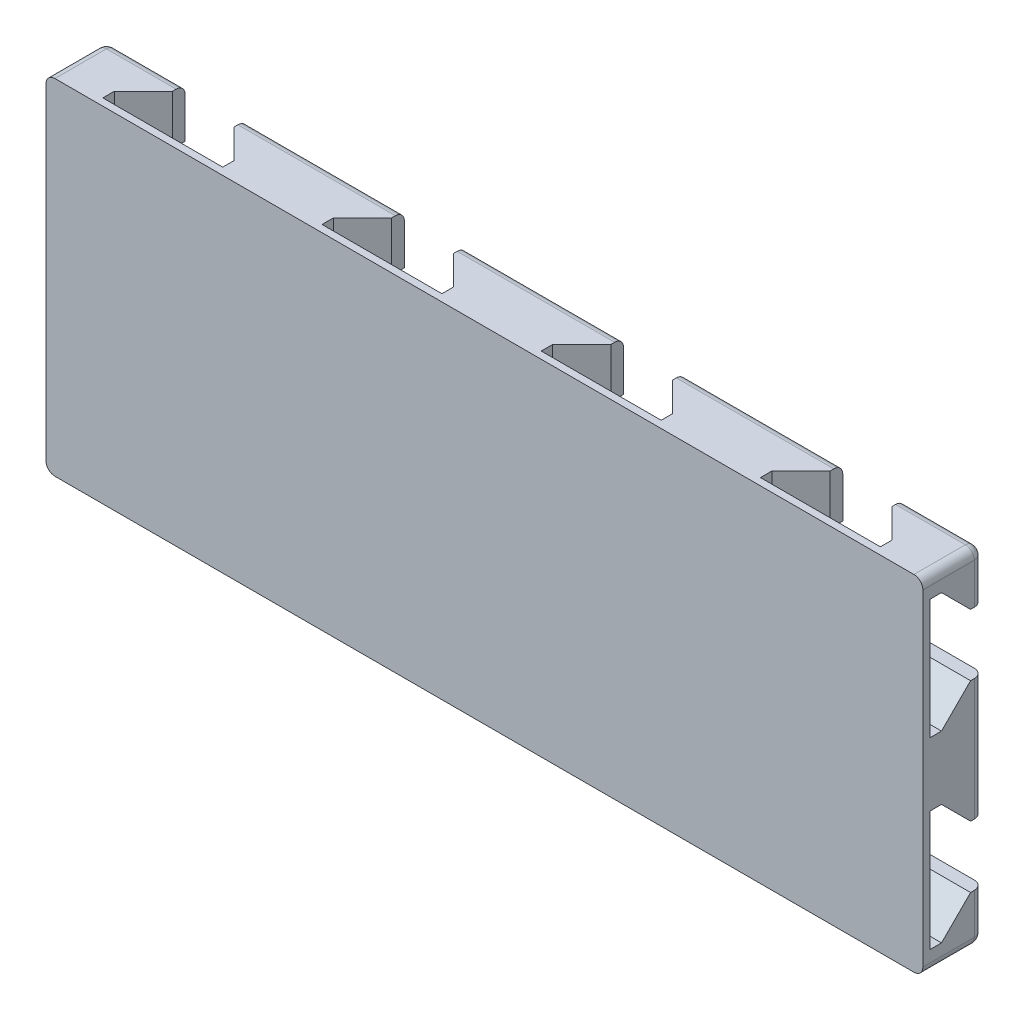
SolidWorks part; units mm, degrees
ref_plane "Front Plane" through (0, 0, 0) normal (1, 0, 0) x (0, 1, 0)
ref_plane "Top Plane" through (0, 0, 0) normal (0, 0, 1) x (0, 1, 0)
ref_plane "Right Plane" through (0, 0, 0) normal (0, 1, 0) x (-1, 0, 0)
sketch "Sketch1" plane through (0, 0, 0) normal (0, 0, 1) x (0, 1, 0)
  line L1 (-38.5, -98) -> (38.5, -98)
  line L2 (-38.5, -98) -> (-38.5, 98)
  line L3 (-38.5, 98) -> (38.5, 98)
  line L4 (38.5, -98) -> (38.5, 98)
  line L5 (-38.5, -98) -> (38.5, 98) construction
  line L6 (-38.5, 98) -> (38.5, -98) construction
  point P0 (0, 0)
  dimension "D1" = 77
  dimension "D2" = 196
extrude "Boss-Extrude1" add sketch "Sketch1" along normal blind 13.5
sketch "Sketch2" plane through (-98, 0, 0) normal (-1, 0, 0) x (0, -1, 0)
  line L0 (0, 0) -> (0, 13.5) construction
  line L1 (7.5, 11.5) -> (7.5, 9.5) construction
  line L2 (7.5, 9.5) -> (14, 3) construction
  line L3 (14, 3) -> (14, 0) construction
  line L4 (-38.5, 0) -> (38.5, 0)
  line L5 (38.5, 0) -> (38.5, 13.5)
  line L6 (38.5, 13.5) -> (-38.5, 13.5)
  line L7 (-38.5, 13.5) -> (-38.5, 0)
  line L8 (-38.5, 0) -> (38.5, 0)
  line L9 (38.5, 0) -> (38.5, 13.5)
  line L10 (38.5, 13.5) -> (-38.5, 13.5)
  line L11 (-38.5, 13.5) -> (-38.5, 0)
  line L12 (33.5, 11.5) -> (33.5, 9.5) construction
  line L13 (33.5, 9.5) -> (27, 3) construction
  line L14 (27, 3) -> (27, 0) construction
  line L15 (7.5, 11.5) -> (33.5, 11.5) construction
  line L16 (27.4, 2.8343) -> (27.4, 0)
  line L17 (33.9, 9.3343) -> (27.4, 2.8343)
  line L18 (33.9, 11.9) -> (33.9, 9.3343)
  line L19 (7.1, 11.9) -> (33.9, 11.9)
  line L20 (7.1, 11.9) -> (7.1, 9.3343)
  line L21 (7.1, 9.3343) -> (13.6, 2.8343)
  line L22 (13.6, 2.8343) -> (13.6, 0)
  line L23 (-13.6, 2.8343) -> (-13.6, 0)
  line L24 (-7.1, 9.3343) -> (-13.6, 2.8343)
  line L25 (-7.1, 11.9) -> (-7.1, 9.3343)
  line L26 (-7.1, 11.9) -> (-33.9, 11.9)
  line L27 (-33.9, 11.9) -> (-33.9, 9.3343)
  line L28 (-33.9, 9.3343) -> (-27.4, 2.8343)
  line L29 (-27.4, 2.8343) -> (-27.4, 0)
  point P14 (13.6328, 0)
  point P17 (13.944, -6.1361)
  dimension "D2" = 135
  dimension "D3" = 135
  dimension "D4" = 2
  dimension "D5" = 6.5
  dimension "D6" = 26
  dimension "D7" = 2
  dimension "D8" = 5
  dimension "D1" = 0
  dimension "D9" = 0.4
extrude "Cut-Extrude1" cut sketch "Sketch2" against normal through all contours L21 L22 L8 L16 L17 L18 L19 L20 | L28 L29 L8 L23 L24 L25 L26 L27 region at (-98, 20.5, 6.8136) region at (-98, -20.5, 6.8136)
sketch "Sketch3" plane through (0, -38.5, 0) normal (0, -1, 0) x (1, 0, 0)
  line L0 (0, 13.5) -> (0, 0) construction
  line L1 (-98, 13.5) -> (98, 13.5) construction
  line L2 (-86.5, 11.5) -> (-60.5, 11.5) construction
  line L3 (-60.5, 11.5) -> (-60.5, 9.5) construction
  line L4 (-60.5, 9.5) -> (-67, 3) construction
  line L5 (-67, 3) -> (-67, 0) construction
  line L6 (-86.5, 11.5) -> (-86.5, 9.5) construction
  line L7 (-86.5, 9.5) -> (-80, 3) construction
  line L8 (-80, 3) -> (-80, 0) construction
  line L10 (-98, 0) -> (98, 0) construction
  line L11 (-98, 13.5) -> (-98, 16) construction
  line L12 (-98, 16) -> (0, 16) construction
  line L13 (0, 16) -> (0, 13.5) construction
  line L14 (-98, 0) -> (98, 0)
  line L15 (98, 0) -> (98, 13.5)
  line L16 (98, 13.5) -> (-98, 13.5)
  line L17 (-98, 13.5) -> (-98, 0)
  line L18 (-98, 0) -> (98, 0)
  line L19 (98, 0) -> (98, 13.5)
  line L20 (98, 13.5) -> (-98, 13.5)
  line L21 (-98, 13.5) -> (-98, 0)
  line L22 (-49, 16) -> (-49, 13.5) construction
  line L23 (-98, 16) -> (-86.5, 11.5) construction
  line L24 (-60.5, 11.5) -> (-49, 16) construction
  line L25 (-80.4, 2.8343) -> (-80.4, 0)
  line L26 (-86.9, 9.3343) -> (-80.4, 2.8343)
  line L27 (-86.9, 11.9) -> (-86.9, 9.3343)
  line L28 (-86.9, 11.9) -> (-60.1, 11.9)
  line L29 (-60.1, 11.9) -> (-60.1, 9.3343)
  line L30 (-60.1, 9.3343) -> (-66.6, 2.8343)
  line L31 (-66.6, 2.8343) -> (-66.6, 0)
  line L32 (-37.9, 11.9) -> (-37.9, 9.3343)
  line L33 (-37.9, 9.3343) -> (-31.4, 2.8343)
  line L34 (-31.4, 2.8343) -> (-31.4, 0)
  line L35 (-17.6, 2.8343) -> (-17.6, 0)
  line L36 (-11.1, 9.3343) -> (-17.6, 2.8343)
  line L37 (-11.1, 11.9) -> (-11.1, 9.3343)
  line L38 (-11.1, 11.9) -> (-37.9, 11.9)
  line L39 (80.4, 2.8343) -> (80.4, 0)
  line L40 (31.4, 2.8343) -> (31.4, 0)
  line L41 (17.6, 2.8343) -> (17.6, 0)
  line L42 (11.1, 9.3343) -> (17.6, 2.8343)
  line L43 (11.1, 11.9) -> (11.1, 9.3343)
  line L44 (11.1, 11.9) -> (37.9, 11.9)
  line L45 (37.9, 11.9) -> (37.9, 9.3343)
  line L46 (37.9, 9.3343) -> (31.4, 2.8343)
  line L47 (66.6, 2.8343) -> (66.6, 0)
  line L48 (60.1, 9.3343) -> (66.6, 2.8343)
  line L49 (60.1, 11.9) -> (60.1, 9.3343)
  line L50 (86.9, 11.9) -> (60.1, 11.9)
  line L51 (86.9, 11.9) -> (86.9, 9.3343)
  line L52 (86.9, 9.3343) -> (80.4, 2.8343)
  line M33 (-98, 0) -> (98, 0)
  dimension "D1" = 135
  dimension "D2" = 135
  dimension "D3" = 6.5
  dimension "D4" = 26
  dimension "D5" = 2
  dimension "D6" = 2
  dimension "D7" = 0.4
  dimension "D9" = 5
  dimension "D8" = 0
extrude "Cut-Extrude2" cut sketch "Sketch3" against normal through all contours L31 L30 L29 L28 L27 L26 L25 L18 | L37 L38 L32 L33 L34 L18 L35 L36 | L46 L45 L44 L43 L42 L41 L18 L40 | L52 L51 L50 L49 L48 L47 L39 M33 region at (-73.5, -38.5, 6.8136) region at (-24.5, -38.5, 6.8136) region at (73.5, -38.5, 6.8136) region at (24.5, -38.5, 6.8136)
fillet "Fillet1" radius 2 20 edges at (0, 38.5, 0) (-49, 38.5, 0) (49, 38.5, 0) (89.2, 38.5, 0) (98, 38.5, 6.75) (98, 32.95, 0) (98, 0, 0) (98, -38.5, 6.75) (98, -32.95, 0) (89.2, -38.5, 0) (49, -38.5, 0) (0, -38.5, 0) (-49, -38.5, 0) (-98, 38.5, 6.75) (-89.2, 38.5, 0) (-98, 32.95, 0) (-98, 0, 0) (-98, -38.5, 6.75) (-98, -32.95, 0) (-89.2, -38.5, 0)
